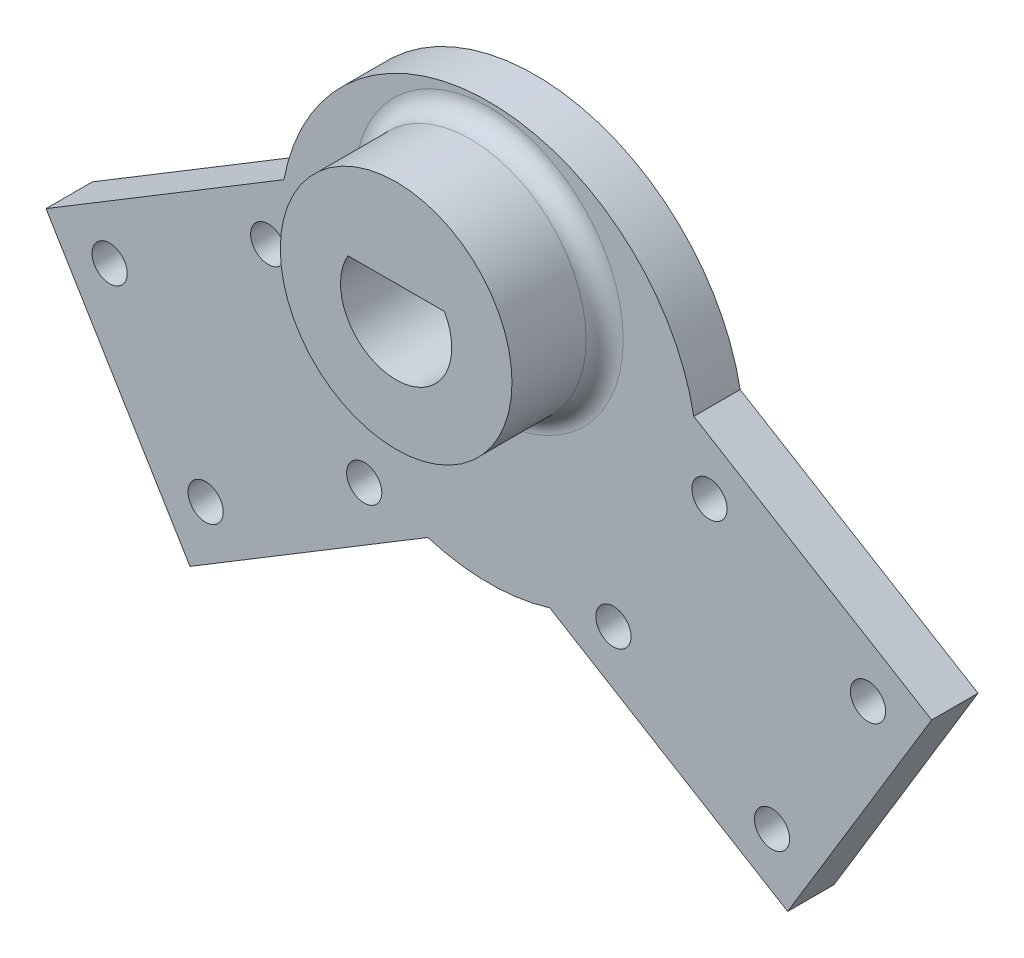
SolidWorks part; units mm, degrees
material "PLA 15%"
ref_plane "Front Plane" through (0, 0, 0) normal (0, 0, 1) x (1, 0, 0)
ref_plane "Top Plane" through (0, 0, 0) normal (0, 1, 0) x (1, 0, 0)
ref_plane "Right Plane" through (0, 0, 0) normal (1, 0, 0) x (0, 0, -1)
sketch "Sketch2" plane through (0, 0, 0) normal (0, 0, 1) x (1, 0, 0)
  line L8 (0, 0) -> (0, -22.5) construction
  line L9 (0, 0) -> (6.5784, -21.5169) construction
  line L10 (0, 0) -> (-6.5784, -21.5169) construction
  line L11 (6.5784, -21.5169) -> (22.1146, 4.1469)
  line L12 (6.5784, -21.5169) -> (32.2421, -37.053)
  line L13 (22.1146, 4.1469) -> (47.7783, -11.3893)
  line L14 (32.2421, -37.053) -> (47.7783, -11.3893)
  line L15 (-6.5784, -21.5169) -> (-22.1146, 4.1469)
  line L16 (-6.5784, -21.5169) -> (-32.2421, -37.053)
  line L17 (-22.1146, 4.1469) -> (-47.7783, -11.3893)
  line L18 (-32.2421, -37.053) -> (-47.7783, -11.3893)
  line L19 (-15.6807, -16.1358) -> (-21.5667, -6.4129) construction
  line L20 (-23.8025, -2.7198) -> (-40.9116, -13.0772) construction
  line L21 (-30.5542, -30.1864) -> (-40.9116, -13.0772) construction
  line L22 (-13.445, -19.8289) -> (-30.5542, -30.1864) construction
  line L23 (13.445, -19.8289) -> (15.6807, -16.1358) construction
  line L24 (23.8025, -2.7198) -> (40.9116, -13.0772) construction
  line L25 (30.5542, -30.1864) -> (40.9116, -13.0772) construction
  line L26 (13.445, -19.8289) -> (30.5542, -30.1864) construction
  line L27 (-21.5667, -6.4129) -> (-23.8025, -2.7198) construction
  line L28 (-13.445, -19.8289) -> (-23.8025, -2.7198) construction
  line L29 (-13.445, -19.8289) -> (-15.6807, -16.1358) construction
  line L30 (15.6807, -16.1358) -> (21.5667, -6.4129) construction
  line L31 (21.5667, -6.4129) -> (23.8025, -2.7198) construction
  line L32 (13.445, -19.8289) -> (23.8025, -2.7198) construction
  line L33 (0, 22.5) -> (0, -22.5) construction
  line L34 (5.1962, 10.5) -> (-5.1962, 10.5)
  arc A0 (-21.5667, -6.4129) -> (-15.6807, -16.1358) centre (0, 0) ccw construction
  arc A1 (-22.1146, 4.1469) -> (-21.5667, -6.4129) centre (0, 0) ccw construction
  arc A2 (-15.6807, -16.1358) -> (-6.5784, -21.5169) centre (0, 0) ccw construction
  arc A3 (-6.5784, -21.5169) -> (6.5784, -21.5169) centre (0, 0) ccw
  arc A4 (15.6807, -16.1358) -> (21.5667, -6.4129) centre (0, 0) ccw construction
  arc A5 (22.1146, 4.1469) -> (-22.1146, 4.1469) centre (0, 0) ccw
  arc A6 (21.5667, -6.4129) -> (22.1146, 4.1469) centre (0, 0) ccw construction
  arc A7 (6.5784, -21.5169) -> (15.6807, -16.1358) centre (0, 0) ccw construction
  arc A8 (-5.1962, 10.5) -> (5.1962, 10.5) centre (0, 7.5) ccw
  arc A9 (-5.1962, 10.5) -> (5.1962, 10.5) centre (0, 7.5) cw construction
  circle A10 centre (0, 7.5) radius 12.5
  point P28 (0, 13.5)
  dimension "D5" = 45
  dimension "D10" = 6
  dimension "D12" = 25
  dimension "D1" = 17
  dimension "D2" = 17
  dimension "D3" = 30
  dimension "D4" = 30
  dimension "D6" = 30
  dimension "D7" = 30
  dimension "D9" = 30
  dimension "D11" = 3
  dimension "D8" = 5
extrude "Boss-Extrude1" add sketch "Sketch2" along normal blind 5 contours L13 A5 L17 L18 L16 A3 L12 L14 A8 L34 | L18 L16 L15 L17 | L12 L14 L13 L11 | A10 A8 L34
hole_wizard "M3 Clearance Hole1" positions "Sketch5" profile "Sketch6" hole size "M3" standard "ANSI Metric" end condition through all
sketch "Sketch5" plane through (0, 0, 5) normal (0, 0, 1) x (1, 0, 0)
  point P0 (-40.9116, -13.0772)
  point P3 (-23.8025, -2.7198)
  point P6 (-13.445, -19.8289)
  point P9 (-30.5542, -30.1864)
  point P12 (13.445, -19.8289)
  point P15 (23.8025, -2.7198)
  point P18 (40.9116, -13.0772)
  point P21 (30.5542, -30.1864)
sketch "Sketch6" plane through (-40.9116, -13.0772, 5) normal (1, 0, 0) x (0, -1, 0)
  line L0 (0, 0) -> (0, 5)
  line L1 (0, 5) -> (1.9, 5)
  line L2 (1.9, 5) -> (1.9, 0)
  line L5 (1.9, 0) -> (0, 0)
  line L11 (0, -6.35) -> (0, 107.95) construction
  dimension "Thru Hole Dia." = 3.8
  dimension "Thru Hole Depth" = 5
extrude "Boss-Extrude3" add sketch "Sketch2<6>" along normal blind 10 from surface contours A10 A8 L34 region at (-12.1464, 7.5, 0) starting at face at (-39.0116, -13.0772, 5)
sketch "Sketch2<6>" plane through (0, 0, 0) normal (0, 0, 1) x (1, 0, 0) same geometry as "Sketch2"
fillet "Fillet1" radius 2 1 edges at (12.5, 7.5, 5)
equation "\"dshaftdistance\"= 0.25"
